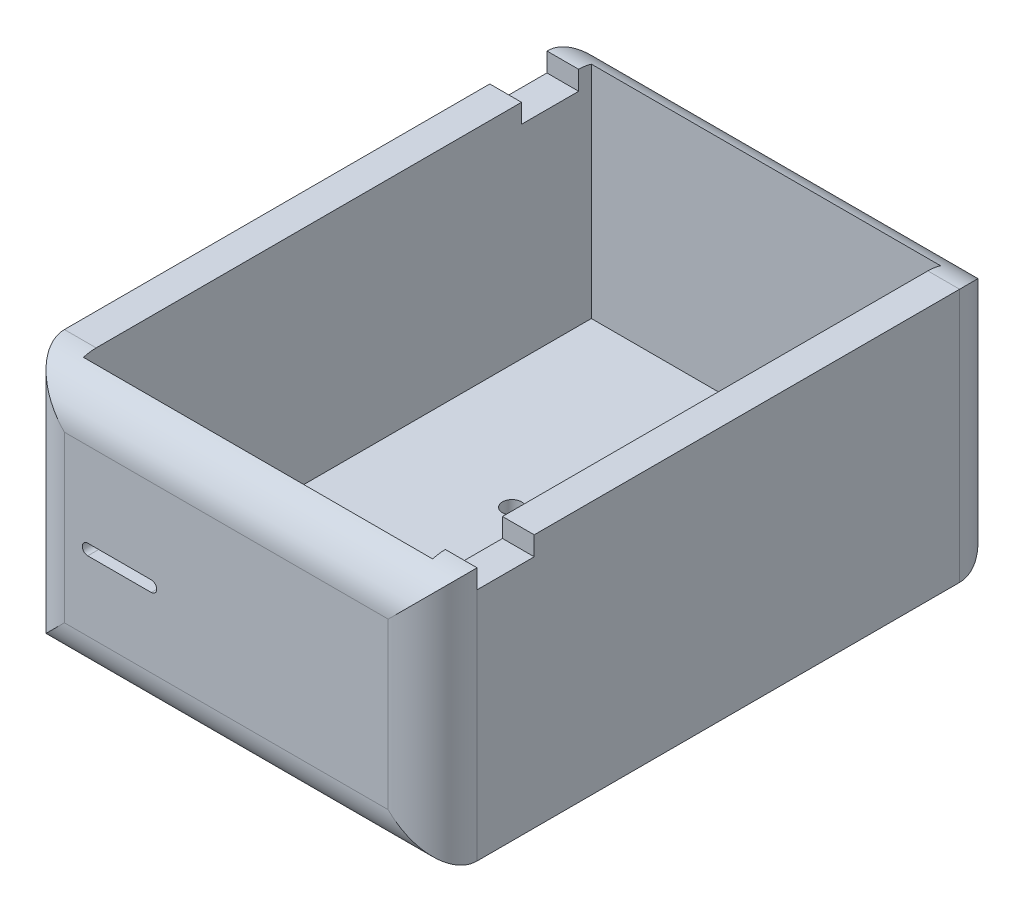
SolidWorks part; units mm, degrees
ref_plane "Plano frontal" through (0, 0, 0) normal (0, 0, 1) x (1, 0, 0)
ref_plane "Plano superior" through (0, 0, 0) normal (0, 1, 0) x (1, 0, 0)
ref_plane "Plano direito" through (0, 0, 0) normal (1, 0, 0) x (0, 0, -1)
sketch "Esboço3" plane through (0, 0, 0) normal (0, 1, 0) x (1, 0, 0)
  line L1 (-32.5, -45) -> (32.5, -45)
  line L2 (-32.5, -45) -> (-32.5, 45)
  line L3 (-32.5, 45) -> (32.5, 45)
  line L4 (32.5, -45) -> (32.5, 45)
  line L5 (-32.5, -45) -> (32.5, 45) construction
  line L6 (-32.5, 45) -> (32.5, -45) construction
  point P1 (0, 0)
  dimension "D1" = 65
  dimension "D2" = 90
extrude "Ressalto-extrusão2" add sketch "Esboço3" along normal blind 40
shell "Casca2" thickness 5 removed face at (0, 40, 0)
sketch "Esboço4" plane through (0, 5, 0) normal (0, 1, 0) x (1, 0, 0)
  line L0 (0, 40) -> (0, -40) construction
  line L2 (27.5, 40) -> (-27.5, 40) construction
  line L4 (-27.5, 0) -> (27.5, 0) construction
  line L5 (-27.5, 40) -> (-27.5, -40) construction
  line L6 (27.5, -40) -> (27.5, 40) construction
  line L7 (-27.5, -40) -> (27.5, -40) construction
  circle A0 centre (-8, 8) radius 1.5
  circle A1 centre (8, 8) radius 1.5
  circle A2 centre (8, -8) radius 1.5
  circle A3 centre (-8, -8) radius 1.5
  dimension "D1" = 8
  dimension "D2" = 8
extrude "Corte-extrusão1" cut sketch "Esboço4" against normal blind 40
fillet "Filete2" radius 7 8 edges at (32.5, 20, -45) (0, 40, -45) (-32.5, 20, -45) (0, 0, -45) (-32.5, 20, 45) (0, 40, 45) (32.5, 20, 45) (0, 0, 45)
sketch "Esboço5" plane through (0, 40, 0) normal (0, 1, 0) x (1, 0, 0)
  line L0 (-27.5, 38) -> (-27.5, -38) construction
  line L1 (-32.5, 38) -> (-27.5, 38)
  line L2 (-32.5, 38) -> (-32.5, 29)
  line L3 (-32.5, 29) -> (-27.5, 29)
  line L4 (-27.5, 38) -> (-27.5, 29)
extrude "Corte-extrusão2" cut sketch "Esboço5" against normal blind 3
sketch "Esboço7" plane through (0, 40, 0) normal (0, 1, 0) x (1, 0, 0)
  line L0 (32.5, -38) -> (32.5, 38) construction
  line L1 (27.5, -38) -> (32.5, -38)
  line L2 (27.5, -38) -> (27.5, -29)
  line L3 (27.5, -29) -> (32.5, -29)
  line L4 (32.5, -38) -> (32.5, -29)
extrude "Corte-extrusão3" cut sketch "Esboço7" against normal blind 3
sketch "Esboço8" plane through (0, 0, 45) normal (0, 0, 1) x (1, 0, 0)
  line L0 (-21.8264, 18.8353) -> (-11.8264, 18.8353) construction
  line L1 (-21.8264, 19.6981) -> (-11.8264, 19.6981)
  line L2 (-21.8264, 17.9726) -> (-11.8264, 17.9726)
  arc A0 (-21.8264, 19.6981) -> (-21.8264, 17.9726) centre (-21.8264, 18.8353) ccw
  arc A1 (-11.8264, 17.9726) -> (-11.8264, 19.6981) centre (-11.8264, 18.8353) ccw
  point P2 (-16.8264, 18.8353)
extrude "Corte-extrusão4" cut sketch "Esboço8" against normal up to next
